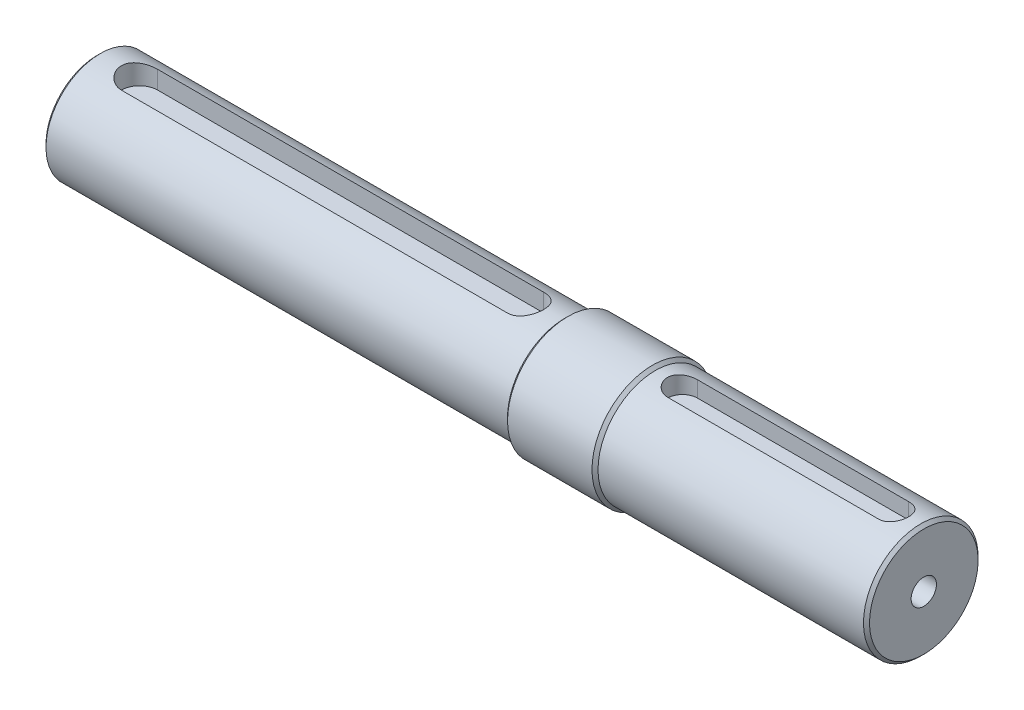
SolidWorks part; units mm, degrees
material "1.0503 (C45)"
ref_plane "前视基准面" through (0, 0, 0) normal (0, 0, 1) x (1, 0, 0)
ref_plane "上视基准面" through (0, 0, 0) normal (0, 1, 0) x (1, 0, 0)
ref_plane "右视基准面" through (0, 0, 0) normal (1, 0, 0) x (0, 0, -1)
sketch "轴轴向刨面" plane through (0, 0, 0) normal (0, 0, 1) x (1, 0, 0)
  line L3 (0, 9) -> (77.5, 9)
  line L4 (77.5, 9) -> (77.5, 10)
  line L5 (77.5, 10) -> (92.5, 10)
  line L6 (92.5, 10) -> (92.5, 9.5)
  line L7 (92.5, 9.5) -> (137, 9.5)
  line L20 (-7.7673, 0) -> (202.2389, 0) construction
  line L21 (0, 9) -> (0, 0)
  line L22 (137, 9.5) -> (137, 0)
  line L23 (0, 0) -> (137, 0)
  dimension "D1" = 44.5
  dimension "D2" = 18
  dimension "D3" = 77.5
  dimension "D4" = 15
  dimension "D5" = 20
  dimension "D6" = 19
revolve "旋转轴" add sketch "轴轴向刨面" angle 360 about L23
ref_plane "9mm键槽面" through (0, 9, 0) normal (0, 1, 0) x (1, 0, 0)
sketch "草图24" plane through (0, 9, 0) normal (0, 1, 0) x (1, 0, 0)
  line L0 (7, 0) -> (71, 0) construction
  line L3 (7, 3) -> (71, 3)
  line L4 (7, -3) -> (71, -3)
  line L7 (0, 9) -> (0, -9) construction
  line L9 (77.5, 10) -> (77.5, -10) construction
  arc A2 (7, 3) -> (7, -3) centre (7, 0) ccw
  arc A3 (71, -3) -> (71, 3) centre (71, 0) ccw
  point P2 (39, 0)
  point P3 (4, 0)
  point P8 (74, 0)
  dimension "D2" = 70
  dimension "D1" = 4
  dimension "D3" = 6
  dimension "D4" = 3.5
extrude "切除-拉伸11" cut sketch "草图24" against normal blind 3.5
ref_plane "9.52mm键槽面" through (0, 9.525, 0) normal (0, 1, 0) x (1, 0, 0)
sketch "草图25" plane through (0, 9.525, 0) normal (0, 1, 0) x (1, 0, 0)
  line L0 (97, 0) -> (132, 0) construction
  line L1 (92.5, 0) -> (137, 0) construction
  line L2 (97, 2.5) -> (132, 2.5)
  line L3 (97, -2.5) -> (132, -2.5)
  line L7 (92.5, -10) -> (92.5, 10) construction
  line L8 (137, -9.5) -> (137, 9.5) construction
  arc A0 (97, 2.5) -> (97, -2.5) centre (97, 0) ccw
  arc A1 (132, -2.5) -> (132, 2.5) centre (132, 0) ccw
  point P5 (114.5, 0)
  point P12 (94.5, 0)
  point P13 (134.5, 0)
  dimension "D2" = 5
  dimension "D1" = 4.5
  dimension "D3" = 40
  dimension "D4" = 35
  dimension "D5" = 5
extrude "切除-拉伸12" cut sketch "草图25" against normal blind 3
hole_wizard "M5 螺纹孔 减速机" positions "草图38" profile "草图37" tap size "M5" standard "GB"
sketch "草图38" plane through (0, 0, 0) normal (1, 0, 0) x (0, 0, -1)
  point P0 (0, 0)
sketch "草图37" plane through (0, 0, 0) normal (0, 1, 0) x (0, 0, 1)
  line L0 (0, 0) -> (0, 29.2618)
  line L1 (0, 29.2618) -> (2.1, 28)
  line L2 (2.1, 28) -> (2.1, 0)
  line L5 (2.1, 0) -> (0, 0)
  line L10 (0, 29.2618) -> (-2.1, 28) construction
  line L11 (0, -6.35) -> (0, 107.95) construction
  dimension "螺纹孔钻头直径" = 4.2
  dimension "螺纹孔钻头深度" = 28
  dimension "导头角度" = 118
cosmetic thread "孔螺蚊线1" parameters "D1"=24, "D2"=5
hole_wizard "M5 螺纹孔 轮毂固定" positions "草图42" profile "草图43" tap size "M5" standard "GB"
sketch "草图42" plane through (137, 0, 0) normal (1, 0, 0) x (0, 0, -1)
  point P0 (0, 0)
cosmetic thread "孔螺蚊线2" parameters "D1"=24, "D2"=5
sketch "草图43" plane through (137, 0, 0) normal (0, 1, 0) x (0, 0, -1)
  line L0 (0, 0) -> (0, 29.2618)
  line L1 (0, 29.2618) -> (2.1, 28)
  line L2 (2.1, 28) -> (2.1, 0)
  line L5 (2.1, 0) -> (0, 0)
  line L10 (0, 29.2618) -> (-2.1, 28) construction
  line L11 (0, -6.35) -> (0, 107.95) construction
  dimension "螺纹孔钻头直径" = 4.2
  dimension "螺纹孔钻头深度" = 28
  dimension "导头角度" = 118
chamfer "倒角3" distance 0.5 angle 45 4 edges at (137, 0, 9.5) (92.5, 0, 10) (77.5, 0, 10) (0, 0, 9)
